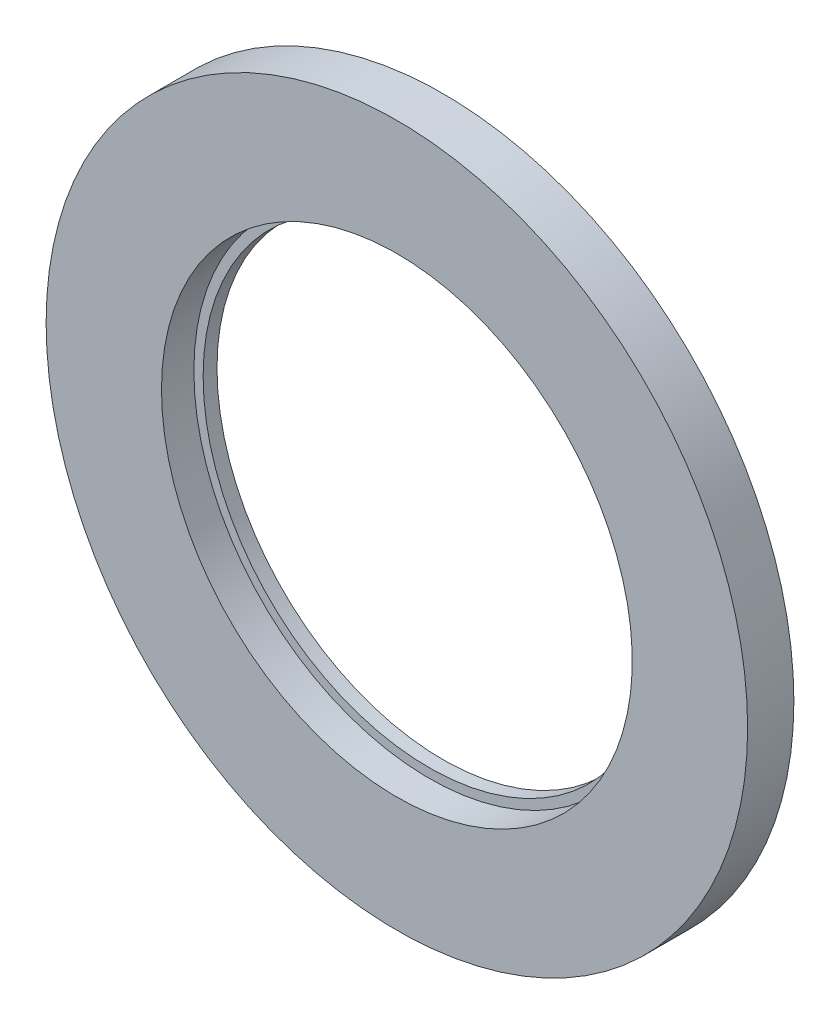
SolidWorks part; units mm, degrees
material "6061 Alloy"
ref_plane "Front Plane" through (0, 0, 0) normal (0, 0, 1) x (1, 0, 0)
ref_plane "Top Plane" through (0, 0, 0) normal (0, 1, 0) x (1, 0, 0)
ref_plane "Right Plane" through (0, 0, 0) normal (1, 0, 0) x (0, 0, -1)
ref_plane "Plane1" through (0, 0, 0) normal (0, -1, 0) x (1, 0, 0)
sketch "Sketch1" plane through (0, 0, 0) normal (0, -1, 0) x (1, 0, 0)
  line L0 (48.9, 0) -> (75.85, 0)
  line L1 (75.85, 0) -> (75.85, 10)
  line L2 (75.85, 10) -> (50.9, 10)
  line L3 (50.9, 10) -> (50.9, 3)
  line L4 (50.9, 3) -> (48.9, 3)
  line L5 (48.9, 3) -> (48.9, 0)
  line L6 (0, 10) -> (0, 0) construction
revolve "Revolve1" add sketch "Sketch1" angle 360 about L6 reverse direction yes
